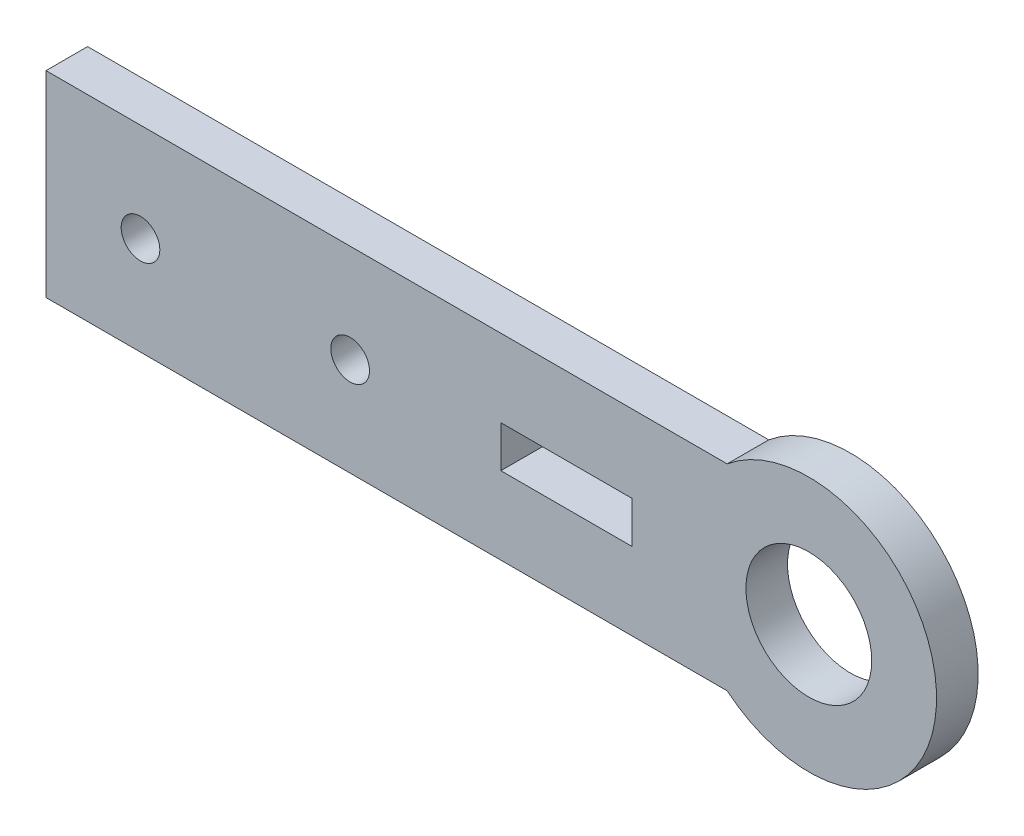
SolidWorks part; units mm, degrees
ref_plane "Front Plane" through (0, 0, 0) normal (0, 0, 1) x (1, 0, 0)
ref_plane "Top Plane" through (0, 0, 0) normal (0, 1, 0) x (1, 0, 0)
ref_plane "Right Plane" through (0, 0, 0) normal (1, 0, 0) x (0, 0, -1)
sketch "Sketch1" plane through (0, 0, 0) normal (0, 0, 1) x (1, 0, 0)
  line L0 (-37.5, 0) -> (37.5, 0)
  line L1 (-37.5, 0) -> (37.5, 0) construction
  line L2 (-37.5, 7.5) -> (37.5, 7.5)
  line L3 (-37.5, -7.5) -> (37.5, -7.5)
  arc A0 (-37.5, 7.5) -> (-37.5, -7.5) centre (-37.5, 0) ccw
  arc A1 (37.5, -7.5) -> (37.5, 7.5) centre (37.5, 0) ccw
  circle A2 centre (-37.5, 0) radius 3.175
  circle A3 centre (37.5, 0) radius 4.8
  point P0 (0, 0)
  point P4 (0, 0)
  dimension "D1" = 6.35
  dimension "D2" = 9.6
  dimension "D3" = 7.5
  dimension "D4" = 75
extrude "Boss-Extrude1" add sketch "Sketch1" along normal blind 3.175 contours L3 A1 L2 A0 A3 A2 region at (0, 6.5876, 0)
sketch "Sketch2" plane through (0, 0, 3.175) normal (0, 0, 1) x (1, 0, 0)
  line L1 (-25, -1.3705) -> (-10, -1.3705)
  line L2 (-25, -1.3705) -> (-25, 1.8045)
  line L3 (-25, 1.8045) -> (-10, 1.8045)
  line L4 (-10, -1.3705) -> (-10, 1.8045)
  line L5 (-25, -1.3705) -> (-10, 1.8045) construction
  line L6 (-25, 1.8045) -> (-10, -1.3705) construction
  line L7 (10, -0.734) -> (25, -0.734)
  line L8 (10, -0.734) -> (10, 2.441)
  line L9 (10, 2.441) -> (25, 2.441)
  line L10 (25, -0.734) -> (25, 2.441)
  line L11 (10, -0.734) -> (25, 2.441) construction
  line L12 (10, 2.441) -> (25, -0.734) construction
  point P0 (-17.5, 0.217)
  point P5 (17.5, 0.8535)
  dimension "D1" = 3.175
  dimension "D2" = 3.175
  dimension "D3" = 15
  dimension "D4" = 15
  dimension "D5" = 20
  dimension "D6" = 10
extrude "Cut-Extrude1" cut sketch "Sketch2" against normal through all contours L2 L1 L4 L3 | L8 L7 L10 L9
sketch "Sketch3" plane through (0, 0, 3.175) normal (0, 0, 1) x (1, 0, 0)
  line L0 (-37.5, 0) -> (-20.71, 0)
  line L2 (-20.71, 0) -> (-56.5053, 0)
  line L3 (-20.71, 0) -> (-20.71, 17.1285)
  line L4 (-20.71, 17.1285) -> (-56.5053, 17.1285)
  line L5 (-56.5053, 0) -> (-56.5053, 17.1285)
  line L6 (-20.71, 0) -> (-56.5053, 0)
  line L7 (-20.71, 0) -> (-20.71, -10.2398)
  line L8 (-20.71, -10.2398) -> (-56.5053, -10.2398)
  line L9 (-56.5053, 0) -> (-56.5053, -10.2398)
  circle M3 centre (-37.5, 0) radius 3.175
  line M4 (-37.5, -7.5) -> (37.5, -7.5)
  line M6 (37.5, 7.5) -> (-37.5, 7.5)
  arc M7 (-37.5, 7.5) -> (-37.5, -7.5) centre (-37.5, 0) ccw
  line M12 (-25, -1.3705) -> (-25, 1.8045)
  line M13 (-25, 1.8045) -> (-10, 1.8045)
  line M15 (-10, -1.3705) -> (-25, -1.3705)
  dimension "D1" = 16.79
extrude "Cut-Extrude2" cut sketch "Sketch3" against normal blind 10 contours L5 L2 L3 L4 M7 M6 | L2 L9 L8 L7 M4 M7 | L3 L2 L0 M13 M6 M7 M3 M12 | L7 L0 L2 M15 M12 M3 M7 M4 region at (-32.0188, 3.9892, 3.175) region at (-31.9038, -3.959, 3.175) region at (-44.2326, -6.4337, 3.175) region at (-41.1018, 10.4693, 3.175)
sketch "Sketch4" plane through (0, 0, 3.175) normal (0, 0, 1) x (1, 0, 0)
  line L0 (-20.71, 1.8045) -> (-20.71, 7.5) construction
  line L1 (-20.71, 2.6568) -> (-9.1283, 2.6568)
  line L2 (-20.71, 2.6568) -> (-20.71, -2.9164)
  line L3 (-20.71, -2.9164) -> (-9.1283, -2.9164)
  line L4 (-9.1283, 2.6568) -> (-9.1283, -2.9164)
extrude "Boss-Extrude2" add sketch "Sketch4" against normal up to surface (3.175 mm away) up to face at (42.3, 0, 0)
sketch "Sketch5" plane through (0, 0, 3.175) normal (0, 0, 1) x (1, 0, 0)
  line L0 (-20.71, 7.5) -> (-20.71, -7.5) construction
  circle A0 centre (-13.5, 0) radius 1.475
  circle A1 centre (2.5, 0) radius 1.475
  dimension "D1" = 7.21
  dimension "D2" = 2.95
  dimension "D3" = 2.95
  dimension "D4" = 16
extrude "Cut-Extrude3" cut sketch "Sketch5" against normal blind 16
sketch "Sketch6" plane through (0, 0, 3.175) normal (0, 0, 1) x (1, 0, 0)
  line L1 (8.271, 4.3719) -> (29.5442, 4.3719)
  line L2 (8.271, 4.3719) -> (8.271, -3.0364)
  line L3 (8.271, -3.0364) -> (29.5442, -3.0364)
  line L4 (29.5442, 4.3719) -> (29.5442, -3.0364)
extrude "Boss-Extrude4" add sketch "Sketch6" against normal up to surface (3.175 mm away) up to face at (-12.025, 0, 0)
sketch "Sketch8" plane through (0, 0, 3.175) normal (0, 0, 1) x (1, 0, 0)
  line L1 (14, -1.5875) -> (24, -1.5875)
  line L2 (14, -1.5875) -> (14, 1.5875)
  line L3 (14, 1.5875) -> (24, 1.5875)
  line L4 (24, -1.5875) -> (24, 1.5875)
  line L5 (14, -1.5875) -> (24, 1.5875) construction
  line L6 (14, 1.5875) -> (24, -1.5875) construction
  point P0 (19, 0)
  dimension "D1" = 14
  dimension "D2" = 3.175
  dimension "D3" = 1.5875
  dimension "D4" = 10
extrude "Cut-Extrude4" cut sketch "Sketch8" against normal blind 10
sketch "Sketch10" plane through (0, 0, 3.175) normal (0, 0, 1) x (1, 0, 0)
  circle A0 centre (37.5, 0) radius 4.75
  circle A1 centre (37.5, 0) radius 9.75
  line M9 (37.5, 7.5) -> (-20.71, 7.5)
  line M11 (-20.71, -7.5) -> (37.5, -7.5)
  arc M12 (37.5, -7.5) -> (37.5, 7.5) centre (37.5, 0) ccw
  dimension "D1" = 9.5
  dimension "D2" = 5
extrude "Boss-Extrude5" add sketch "Sketch10" against normal up to surface (3.175 mm away) contours A1 M11 M9 M12 region at (41.5354, -8.598, 3.175) up to face at (19, 0, 0)
